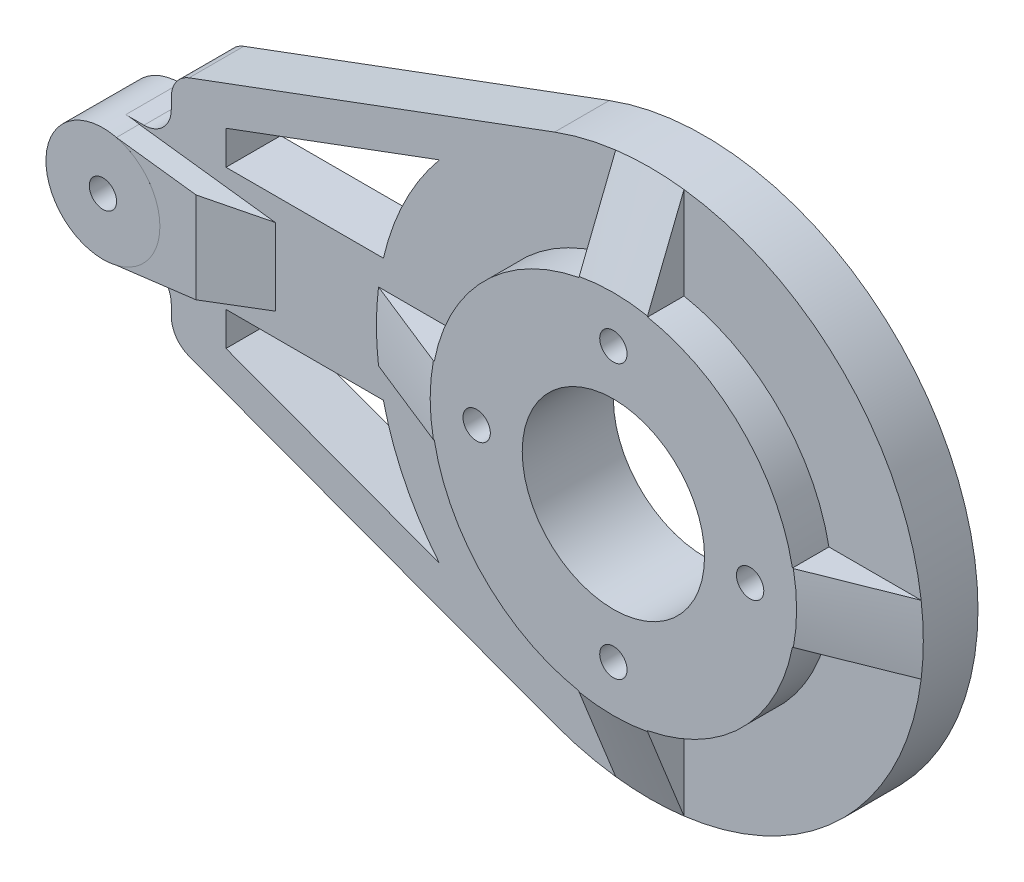
SolidWorks part; units mm, degrees
ref_plane "Front Plane" through (0, 0, 0) normal (0, 0, 1) x (1, 0, 0)
ref_plane "Top Plane" through (0, 0, 0) normal (0, 1, 0) x (1, 0, 0)
ref_plane "Right Plane" through (0, 0, 0) normal (1, 0, 0) x (0, 0, -1)
sketch "Sketch2" plane through (0, 0, 0) normal (0, 0, 1) x (1, 0, 0)
  circle A0 centre (0, 0) radius 20
  circle A1 centre (0, 0) radius 40
  dimension "D1" = 40
  dimension "D2" = 80
extrude "Boss-Extrude1" add sketch "Sketch2" along normal blind 8
sketch "Sketch3" plane through (0, 0, 0) normal (0, 0, -1) x (-1, 0, 0)
  line L0 (0, 0) -> (105, 0) construction
  line L1 (105, -25) -> (105, 25)
  line L2 (105, 25) -> (20.8942, 56.2444)
  line L3 (105, -25) -> (20.8942, -56.2444)
  arc A0 (20.8942, 56.2444) -> (20.8942, -56.2444) centre (0, 0) ccw
  circle A1 centre (0, 0) radius 20
  point P7 (105, 0)
  dimension "D1" = 120
  dimension "D2" = 105
  dimension "D3" = 50
extrude "Boss-Extrude2" add sketch "Sketch3" along normal blind 12
sketch "Sketch4" plane through (0, 0, -12) normal (0, 0, -1) x (-1, 0, 0)
  line L0 (0, 0) -> (0, 30) construction
  circle A0 centre (0, 30) radius 7.5
  circle A1 centre (30, 0) radius 7.5
  circle A2 centre (0, -30) radius 7.5
  circle A3 centre (-30, 0) radius 7.5
  point P13 (0, 0)
  dimension "D2" = 15
  dimension "D1" = 30
  dimension "D3" = 4
extrude "Cut-Extrude1" cut sketch "Sketch4" against normal blind 10
sketch "Sketch5" plane through (0, 0, -2) normal (0, 0, -1) x (-1, 0, 0)
  circle A0 centre (30, 0) radius 3
  circle A1 centre (0, -30) radius 3
  circle A2 centre (-30, 0) radius 3
  circle A3 centre (0, 30) radius 3
  point P12 (0, 0)
  dimension "D1" = 6
  dimension "D2" = 4
extrude "Cut-Extrude2" cut sketch "Sketch5" against normal blind 29
sketch "Sketch6" plane through (0, 0, 0) normal (0, 0, 1) x (1, 0, 0)
  line L0 (39.2906, -7.5) -> (59.5294, -7.5)
  line L1 (39.2906, 7.5) -> (59.5294, 7.5)
  line L2 (-7.5, 39.2906) -> (-7.5, 59.5294)
  line L3 (7.5, 39.2906) -> (7.5, 59.5294)
  line L4 (-7.5, -39.2906) -> (-7.5, -59.5294)
  line L5 (7.5, -39.2906) -> (7.5, -59.5294)
  line L6 (-39.2906, 7.5) -> (-59.5294, 7.5)
  line L7 (-39.2906, -7.5) -> (-59.5294, -7.5)
  arc A1 (7.5, 39.2906) -> (-7.5, 39.2906) centre (0, 0) ccw
  arc A5 (7.5, 59.5294) -> (-7.5, 59.5294) centre (0, 0) ccw
  arc A6 (59.5294, -7.5) -> (59.5294, 7.5) centre (0, 0) ccw
  arc A7 (39.2906, -7.5) -> (39.2906, 7.5) centre (0, 0) ccw
  arc A8 (-7.5, -59.5294) -> (7.5, -59.5294) centre (0, 0) ccw
  arc A9 (-7.5, -39.2906) -> (7.5, -39.2906) centre (0, 0) ccw
  arc A10 (-59.5294, 7.5) -> (-59.5294, -7.5) centre (0, 0) ccw
  arc A11 (-39.2906, 7.5) -> (-39.2906, -7.5) centre (0, 0) ccw
  point P10 (0, 48.2861)
  point P13 (-7.5, 49.41)
  point P16 (7.5, 49.41)
  point P25 (0, 0)
  dimension "D1" = 15
  dimension "D2" = 4
extrude "Boss-Extrude3" add sketch "Sketch6" along direction (0, 0, 1) on the side of the normal blind 8
chamfer "Chamfer3" distance 8 angle 68 4 edges at (0, 60, 8) (60, 0, 8) (-60, 0, 8) (0, -60, 8) first distance on face at (15.8462, 0, 1.5) first distance on face at (-59.7647, 0, 4)
sketch "Sketch7" plane through (0, 0, -12) normal (0, 0, -1) x (-1, 0, 0)
  line L0 (105, 0) -> (115, 0) construction
  line L1 (105, -25) -> (105, 25) construction
  line L2 (115, 12.5) -> (105, 12.5)
  line L3 (105, 12.5) -> (105, -12.5)
  line L4 (105, -12.5) -> (115, -12.5)
  arc A0 (115, -12.5) -> (115, 12.5) centre (115, 0) ccw
  dimension "D2" = 25
  dimension "D1" = 10
extrude "Boss-Extrude4" add sketch "Sketch7" against normal up to surface (12 mm away) up to face at (-40.8222, 0, 0)
fillet "Fillet1" radius 6 4 edges at (-105, 25, -6) (-105, 12.5, -6) (-105, -25, -6) (-105, -12.5, -6)
sketch "Sketch8" plane through (0, 0, -12) normal (0, 0, -1) x (-1, 0, 0)
  line L1 (118.7786, 6.485) -> (111.2731, 6.5149)
  line L2 (111.2731, 6.5149) -> (107.4945, 0.0298)
  line L3 (107.4945, 0.0298) -> (111.2214, -6.485)
  line L4 (111.2214, -6.485) -> (118.7269, -6.5149)
  line L5 (118.7269, -6.5149) -> (122.5055, -0.0298)
  line L6 (122.5055, -0.0298) -> (118.7786, 6.485)
  circle A0 centre (115, 0) radius 6.5 construction
  dimension "D1" = 13
extrude "Cut-Extrude3" cut sketch "Sketch8" against normal blind 10
sketch "Sketch9" plane through (0, 0, -2) normal (0, 0, -1) x (-1, 0, 0)
  circle A0 centre (115, 0) radius 3
  dimension "D1" = 6
extrude "Cut-Extrude4" cut sketch "Sketch9" against normal blind 6
sketch "Sketch10" plane through (0, 0, 0) normal (0, 0, 1) x (1, 0, 0)
  line L2 (-20.8942, -56.2444) -> (-101.0894, -26.4527) construction
  line L3 (-58.4615, -13.5) -> (-93, -13.5)
  line L4 (-59.5294, -7.5) -> (-39.2906, -7.5) construction
  line L6 (-93, -13.5) -> (-93, -20.9237)
  line L7 (-60, 0) -> (-127.5, 0) construction
  line L9 (-93, 20.9237) -> (-46.1679, 38.3213)
  line L10 (-93, 13.5) -> (-93, 20.9237)
  line L11 (-93, -20.9237) -> (-46.1679, -38.3213)
  line L12 (-58.4615, 13.5) -> (-93, 13.5)
  arc A0 (-58.4615, -13.5) -> (-46.1679, -38.3213) centre (0, 0) ccw
  arc A2 (-59.5294, 7.5) -> (-59.5294, -7.5) centre (0, 0) ccw construction
  arc A3 (-115, 12.5) -> (-115, -12.5) centre (-115, 0) ccw construction
  arc A4 (-58.4615, 13.5) -> (-46.1679, 38.3213) centre (0, 0) cw
  dimension "D1" = 60
  dimension "D3" = 8
  dimension "D4" = 6
extrude "Cut-Extrude5" cut sketch "Sketch10" against normal blind 22
sketch "Sketch11" plane through (0, 0, -12) normal (0, 0, -1) x (-1, 0, 0)
  point P0 (0, 0)
sketch "Sketch12" plane through (0, 0, 0) normal (0, 0, 1) x (1, 0, 0)
  circle A0 centre (-115, 0) radius 3
  circle A1 centre (-115, 0) radius 12.5
extrude "Boss-Extrude5" add sketch "Sketch12" along normal blind 5
sketch "Sketch13" plane through (0, 0, 0) normal (0, 0, 1) x (1, 0, 0)
  line L0 (-74.7433, 7.5) -> (-112.0372, 12.1444)
  line L6 (-74.7433, 7.5) -> (-74.7433, -7.5)
  line L7 (-74.7433, -7.5) -> (-112.0372, -12.1444)
  arc A2 (-112.0372, -12.1444) -> (-112.0372, 12.1444) centre (-115, 0) ccw
extrude "Boss-Extrude6" add sketch "Sketch13" along normal blind 5
chamfer "Chamfer7" distance 8 angle 68 1 edges at (-74.7433, 0, 5) first distance on face at (-74.7433, 0, 2.5)
